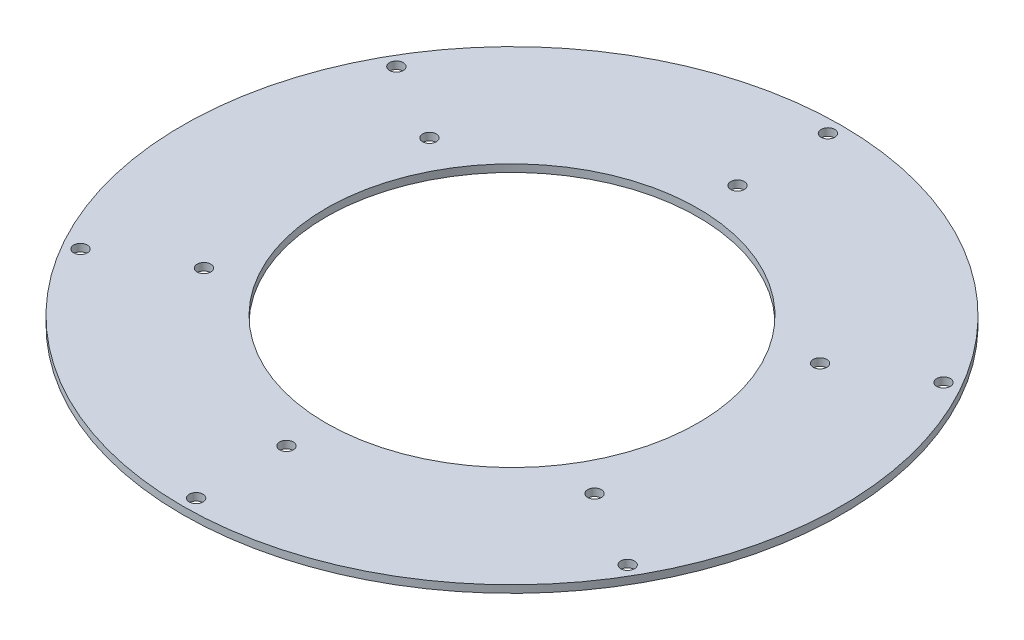
SolidWorks part; units mm, degrees
ref_plane "Front Plane" through (0, 0, 0) normal (0, 0, 1) x (1, 0, 0)
ref_plane "Top Plane" through (0, 0, 0) normal (0, 1, 0) x (1, 0, 0)
ref_plane "Right Plane" through (0, 0, 0) normal (1, 0, 0) x (0, 0, -1)
sketch "Sketch1" plane through (0, 0, 0) normal (0, 1, 0) x (1, 0, 0)
  line L0 (0, 70.8759) -> (0, 65) construction
  line L1 (0, 57) -> (0, 40) construction
  line L2 (0, -57) -> (0, -40) construction
  circle A0 centre (0, 0) radius 67.5 construction
  circle A1 centre (0, 67.938) radius 1.4732
  circle A2 centre (58.836, 33.969) radius 1.4732
  circle A3 centre (58.836, -33.969) radius 1.4732
  circle A4 centre (0, -67.938) radius 1.4732
  circle A5 centre (-58.836, -33.969) radius 1.4732
  circle A6 centre (-58.836, 33.969) radius 1.4732
  circle A7 centre (0, 0) radius 65
  circle A8 centre (0, 0) radius 70.8759
  circle A9 centre (0, 67.938) radius 2.3241 construction
  circle A10 centre (0, 0) radius 57
  circle A11 centre (0, 0) radius 40
  circle A12 centre (-76.2, 0) radius 2.3241 construction
  circle A13 centre (76.2, 0) radius 2.3241 construction
  circle A14 centre (0, 0) radius 76.2 construction
  circle A15 centre (0, 48.5) radius 1.4732
  circle A16 centre (42.0022, 24.25) radius 1.4732
  circle A17 centre (42.0022, -24.25) radius 1.4732
  circle A18 centre (0, -48.5) radius 1.4732
  circle A19 centre (-42.0022, -24.25) radius 1.4732
  circle A20 centre (-42.0022, 24.25) radius 1.4732
  point P17 (0, 0)
  point P32 (0, 0)
  point P43 (0, 0)
  dimension "D2" = 2.9464
  dimension "D5" = 130
  dimension "D7" = 4.6482
  dimension "D9" = 80
  dimension "D6" = 4.6482
  dimension "D8" = 8
  dimension "D10" = 152.4
  dimension "D11" = 76.2
  dimension "D12" = 5.3241
  dimension "D3" = 6
  dimension "D13" = 6
extrude "Boss-Extrude1" add sketch "Sketch1" along normal blind 1.6 contours A8 A1 A2 A3 A4 A5 A6 A7 | A7 A10 | A10 A11 region at (-63.1615, 0, 0) region at (-68.8712, 0, 0) region at (-55.3878, 0, 0)
extrude "Cut-Extrude1" cut sketch "Sketch1<3>" along normal blind 0.1 contours A7 A10 region at (-63.1615, 0, 0)
sketch "Sketch1<3>" plane through (0, 0, 0) normal (0, 1, 0) x (1, 0, 0) same geometry as "Sketch1"
equation "\"D2@Sketch1\"=0.1160in"
equation "\"D11@Sketch1\"=\"D10@Sketch1\"/2"
equation "\"D12@Sketch1\"=(\"D6@Sketch1\"/2)+3"
